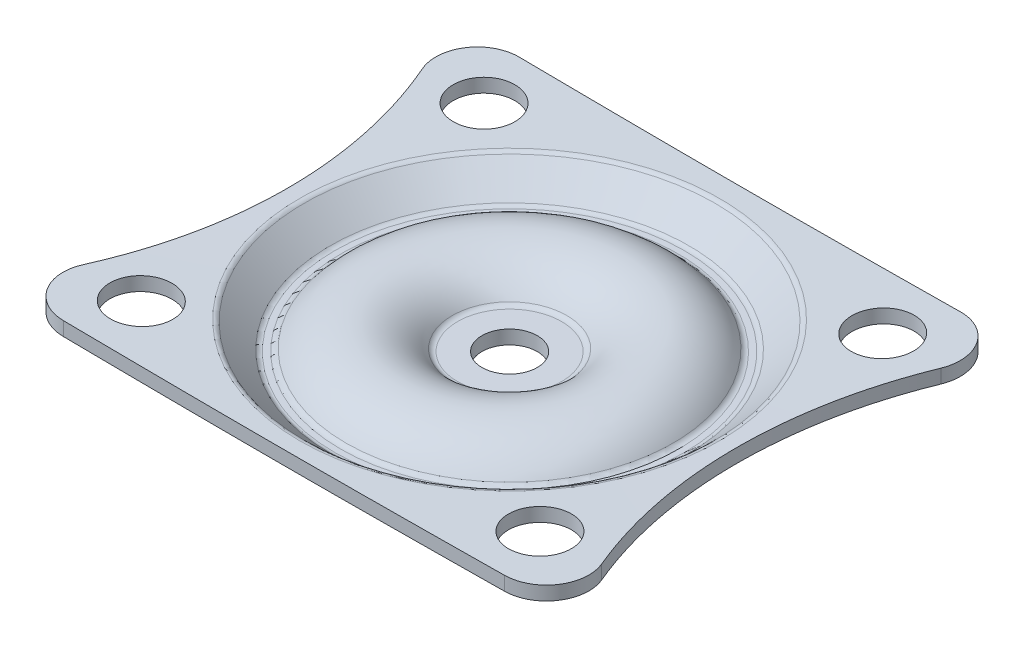
SolidWorks part; units mm, degrees
ref_plane "Alzado" through (0, 0, 0) normal (0, 0, 1) x (1, 0, 0)
ref_plane "Planta" through (0, 0, 0) normal (0, 1, 0) x (1, 0, 0)
ref_plane "Vista lateral" through (0, 0, 0) normal (1, 0, 0) x (0, 0, -1)
sketch "Croquis1" plane through (0, 0, 0) normal (0, 0, 1) x (1, 0, 0)
  line L0 (3.7638, 0) -> (0, 0)
  line L1 (0, -1) -> (15, -1) construction
  line L2 (4.0072, 0) -> (4.0072, 2) construction
  line L3 (12.2252, 0) -> (12.6505, 0)
  line L4 (12.9908, 0.1337) -> (14.8594, 1.8694)
  line L5 (15.1919, 2.003) -> (30.5258, 2.2437)
  line L6 (8, -1) -> (8, 3.9942) construction
  line L7 (4.0072, 2) -> (15, 2) construction
  line L8 (15, -1) -> (15, 4.7358) construction
  line L9 (15.5913, 1.0092) -> (30.5415, 1.2438)
  line L10 (13.6713, -0.599) -> (15.2588, 0.8756)
  line L11 (12.2252, -1) -> (12.6505, -1)
  line L12 (3.7638, -1) -> (0, -1)
  line L13 (30.5258, 2.2437) -> (30.5415, 1.2438)
  line L14 (0, 0) -> (0, -1)
  line L15 (0, -1) -> (0, -11.4008) construction
  line L16 (15.3994, 1.0061) -> (30.5415, 1.2438) construction
  line L17 (13.6713, -0.599) -> (15.3994, 1.0061) construction
  arc A0 (11.8388, 0.1827) -> (4.1502, 0.1827) centre (7.9945, -2.9746) ccw
  arc A1 (4.1502, 0.1827) -> (3.7638, 0) centre (3.7638, 0.5) cw
  arc A2 (12.2252, 0) -> (11.8388, 0.1827) centre (12.2252, 0.5) cw
  arc A3 (15.1919, 2.003) -> (14.8594, 1.8694) centre (15.1997, 1.5031) ccw
  arc A4 (12.9908, 0.1337) -> (12.6505, 0) centre (12.6505, 0.5) cw
  arc A6 (13.6713, -0.599) -> (12.6505, -1) centre (12.6505, 0.5) cw
  arc A7 (12.2252, -1) -> (11.066, -0.452) centre (12.2252, 0.5) cw
  arc A8 (11.066, -0.452) -> (4.923, -0.452) centre (7.9945, -2.9746) ccw
  arc A9 (4.923, -0.452) -> (3.7638, -1) centre (3.7638, 0.5) cw
  arc A10 (15.5913, 1.0092) -> (15.2588, 0.8756) centre (15.5991, 0.5092) ccw
  arc A11 (15.3994, 1.0061) -> (15.3994, 1.0061) centre (15.3994, 1.0061) ccw construction
  dimension "D3" = 15
  dimension "D4" = 0.5
  dimension "D5" = 1
  dimension "D1" = 0.5
  dimension "D2" = 0.5
  dimension "D6" = 0.5
revolve "Revolución1" add sketch "Croquis1" angle 360 about L15
sketch "Croquis2" plane through (0, 0, 0) normal (0, 1, 0) x (1, 0, 0)
  line L0 (-16.25, 0.1743) -> (16.25, 0.1743) construction
  line L1 (-0.5468, 16.6743) -> (0, 0.1743) construction
  line L2 (-15.9602, -16.3257) -> (15.9602, -16.3257)
  line L3 (15.9602, 16.6743) -> (-15.9602, 16.6743)
  line L5 (-41.8276, 36.0763) -> (41.8276, 36.0763)
  line L6 (-41.8276, 36.0763) -> (-41.8276, -35.7277)
  line L7 (-41.8276, -35.7277) -> (41.8276, -35.7277)
  line L8 (41.8276, 36.0763) -> (41.8276, -35.7277)
  line L9 (-41.8276, 36.0763) -> (41.8276, -35.7277) construction
  line L10 (-41.8276, -35.7277) -> (41.8276, 36.0763) construction
  circle A0 centre (-14.4226, 12.5743) radius 2.25
  circle A1 centre (-14.4226, -12.2257) radius 2.253
  arc A2 (-18.7564, -12.0936) -> (-15.9602, -16.3257) centre (-15.9602, -13.2859) ccw
  arc A3 (15.9602, -16.3257) -> (18.7564, -12.0936) centre (15.9602, -13.2859) ccw
  arc A4 (18.7564, 12.4422) -> (18.7564, -12.0936) centre (47.5265, 0.1743) ccw
  arc A5 (18.7564, 12.4422) -> (15.9602, 16.6743) centre (15.9602, 13.6345) ccw
  arc A6 (-15.9602, 16.6743) -> (-18.7564, 12.4422) centre (-15.9602, 13.6345) ccw
  arc A7 (-18.7564, -12.0936) -> (-18.7564, 12.4422) centre (-47.5265, 0.1743) ccw
  circle A8 centre (14.4226, -12.2257) radius 2.253
  circle A9 centre (14.4226, 12.5743) radius 2.25
  dimension "D1" = 4.5
  dimension "D2" = 28.8451
  dimension "D3" = 24.8
  dimension "D4" = 28.8451
  dimension "D5" = 24.8
extrude "Cortar-Extruir4" cut sketch "Croquis2" along normal blind 10 contours L8 L5 L6 L7 A2 A7 A6 L3 A5 A4 A3 L2 region at (0, 0, -34.9739)
extrude "Cortar-Extruir5" cut sketch "Croquis2<6>" along normal blind 10 contours A0 | A1 | A8 | A9 region at (-14.4226, 0, -12.5743) region at (-14.4226, 0, 12.2257) region at (14.4226, 0, 12.2257) region at (14.4226, 0, -12.5743)
sketch "Croquis2<6>" plane through (0, 0, 0) normal (0, 1, 0) x (1, 0, 0) same geometry as "Croquis2"
sketch "Croquis3" plane through (0, 0, 0) normal (0, 1, 0) x (1, 0, 0)
  circle A0 centre (0, 0) radius 2
extrude "Cortar-Extruir6" cut sketch "Croquis3" against normal blind 10
ref_plane "Plano1" through (0, 2.0196, 0) normal (0, 1, 0) x (1, 0, 0)
sketch "Croquis4" plane through (0, 2.0196, 0) normal (0, 1, 0) x (1, 0, 0)
  line L0 (-16.25, 0.1743) -> (16.25, 0.1743)
  arc A0 (-18.7564, -12.0936) -> (-18.7564, 12.4422) centre (-47.5265, 0.1743) ccw construction
  arc A1 (18.7564, 12.4422) -> (18.7564, -12.0936) centre (47.5265, 0.1743) ccw construction
